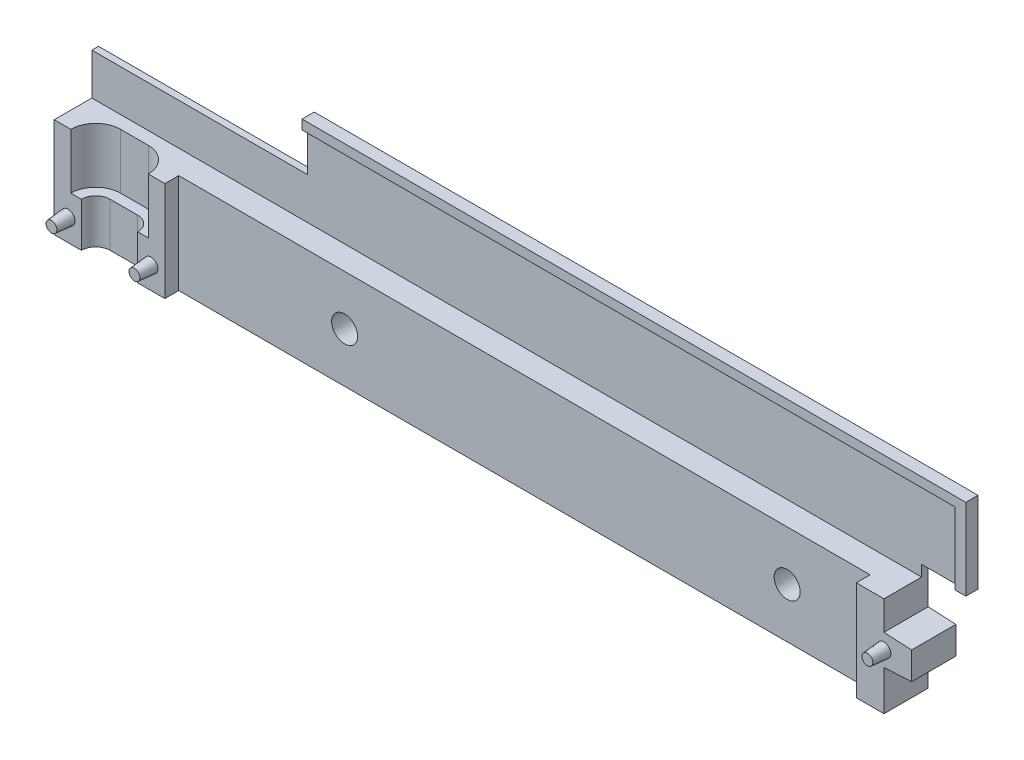
SolidWorks part; units mm, degrees
ref_plane "Front Plane" through (0, 0, 0) normal (0, 0, 1) x (1, 0, 0)
ref_plane "Top Plane" through (0, 0, 0) normal (0, 1, 0) x (1, 0, 0)
ref_plane "Right Plane" through (0, 0, 0) normal (1, 0, 0) x (0, 0, -1)
ref_axis "X-Axis" through (0, 0, 0) along (1, 0, 0)
ref_axis "Y-Axis" through (0, 42.2917, 0) along (0, -1, 0)
ref_axis "Z-Axis" through (0, 0, 55.0015) along (0, 0, -1)
sketch "Sketch1" plane through (0, 0, 0) normal (0, 0, 1) x (1, 0, 0)
  line L1 (-127.8191, -9.8629) -> (22.1809, -9.8629)
  line L2 (22.1809, -9.8629) -> (22.1809, -2.6129)
  line L3 (22.1809, -2.6129) -> (27.1809, -2.6129)
  line L4 (27.1809, -2.6129) -> (27.1809, 2.8871)
  line L5 (27.1809, 2.8871) -> (22.1809, 2.8871)
  line L6 (22.1809, 2.8871) -> (22.1809, 10.1371)
  line L7 (22.1809, 10.1371) -> (31.1809, 10.1371)
  line L8 (31.1809, 10.1371) -> (31.1809, 23.6371)
  line L10 (-127.8191, 15.6371) -> (-127.8191, -9.8629)
  line L12 (-88.8191, -25.8695) -> (-88.8191, 48.9262) construction
  line L13 (31.1809, 13.1371) -> (10.3885, 13.1371) construction
  line L14 (31.1809, 23.6371) -> (-88.8191, 23.6371) construction
  line L15 (-88.8191, 23.6371) -> (-88.8191, 15.6371)
  line L16 (-88.8191, 15.6371) -> (-127.8191, 15.6371)
  line L17 (31.1809, 23.6371) -> (31.1809, 24.8371)
  line L18 (31.1809, 24.8371) -> (-88.8191, 24.8371)
  line L19 (-88.8191, 24.8371) -> (-88.8191, 23.6371)
  point P5 (27.1809, 0.1371)
  dimension "D2" = 10
  dimension "D3" = 20
  dimension "D4" = 5.5
  dimension "D5" = 9
  dimension "D7" = 120
  dimension "D8" = 5
  dimension "D10" = 3
  dimension "D11" = 8
  dimension "D12" = 10.5
  dimension "D13" = 1.2
  dimension "D14" = 150
extrude "Boss-Extrude1" add sketch "Sketch1" along normal blind 8 and the other way blind 8
sketch "Sketch2" plane through (-127.8191, 0, 0) normal (-1, 0, 0) x (0, 0, 1)
  line L0 (-8, -9.8629) -> (8, -9.8629) construction
  line L1 (-6.8, 23.1371) -> (6.8, 23.1371) construction
  line L2 (-6.8, 23.1371) -> (-6.8, 8.1371)
  line L3 (-6.8, 8.1371) -> (6.8, 8.1371)
  line L4 (6.8, 23.1371) -> (6.8, 8.1371)
  line L5 (-8, 24.8371) -> (-8, 15.6371) construction
  line L7 (-8, 2.8871) -> (8, 2.8871) construction
  line L8 (-8, 15.6371) -> (-8, -9.8629) construction
  line L9 (8, 15.6371) -> (8, -9.8629) construction
  line L10 (0, 2.8871) -> (0, 23.1371) construction
  line L11 (-6.8, 23.1371) -> (-5.8, 23.1371)
  line L12 (-5.8, 23.1371) -> (-5.8, 24.8371)
  line L13 (-8, 24.8371) -> (8, 24.8371) construction
  line L14 (-5.8, 24.8371) -> (5.8, 24.8371)
  line L15 (5.8, 24.8371) -> (5.8, 23.1371)
  line L16 (5.8, 23.1371) -> (6.8, 23.1371)
  point P6 (0, 23.1371)
  dimension "D1" = 33
  dimension "D2" = 18
  dimension "D3" = 1
  dimension "D4" = 1
  dimension "D5" = 15
  dimension "D7" = 1.2
extrude "Cut-Extrude1" cut sketch "Sketch2" against normal offset from surface (157 mm away) 2 up to face at (31.1809, 17.4871, 0)
sketch "Sketch8" plane through (0, 0, 0) normal (0, 0, 1) x (1, 0, 0)
  line L0 (-127.8191, 15.6371) -> (-127.8191, -9.8629) construction
  line L1 (-107.8191, 24.8371) -> (17.1809, 24.8371)
  line L2 (-107.8191, 24.8371) -> (-107.8191, -9.8629)
  line L3 (-107.8191, -9.8629) -> (17.1809, -9.8629)
  line L4 (17.1809, 24.8371) -> (17.1809, -9.8629)
  line L5 (-127.8191, -9.8629) -> (22.1809, -9.8629) construction
  line L7 (22.1809, 2.8871) -> (22.1809, 10.1371) construction
  line L8 (29.1809, 24.8371) -> (-88.8191, 24.8371) construction
  point P12 (22.1809, 6.5121)
  dimension "D1" = 20
  dimension "D2" = 5
extrude "Cut-Extrude4" cut sketch "Sketch8" against normal blind 2.5 and the other way blind 2.5 contours L2 L3 L4 L1
sketch "Sketch9" plane through (0, 0, 0) normal (0, 0, 1) x (1, 0, 0)
  line L0 (-107.8191, -0.8629) -> (17.1809, -0.8629) construction
  line L1 (-107.8191, 8.1371) -> (-107.8191, -9.8629) construction
  line L2 (17.1809, 8.1371) -> (17.1809, -9.8629) construction
  circle A0 centre (-77.8191, -0.8629) radius 2.35
  circle A1 centre (2.1809, -0.8629) radius 2.35
  dimension "D1" = 4.7
  dimension "D2" = 80
  dimension "D3" = 15
extrude "Cut-Extrude5" cut sketch "Sketch9" against normal through all and the other way through all
chamfer "Chamfer2" distance 5 angle 3 2 edges at (27.1809, -2.6129, 0) (27.1809, 2.8871, 0) first distance on face at (24.6809, -2.6129, 0) first distance on face at (24.6809, 2.8871, 0)
sketch "Sketch14" plane through (0, 8.1371, 0) normal (0, 1, 0) x (1, 0, 0)
  line L0 (-120.3191, 4.5) -> (-115.3191, 4.5)
  line L1 (-115.3191, -4.5) -> (-120.3191, -4.5)
  line L2 (-107.8191, 0) -> (-127.8191, 0) construction
  line L3 (-107.8191, 2.5) -> (-107.8191, -2.5) construction
  line L5 (-127.8191, 6.8) -> (-127.8191, -6.8) construction
  arc A0 (-115.3191, 4.5) -> (-115.3191, -4.5) centre (-115.3191, 0) cw
  arc A1 (-120.3191, -4.5) -> (-120.3191, 4.5) centre (-120.3191, 0) cw
  point P16 (-117.8191, 0)
  dimension "D1" = 4.5
  dimension "D2" = 5
  dimension "D3" = 2.5
extrude "Cut-Extrude8" cut sketch "Sketch14" against normal blind 10
sketch "Sketch15" plane through (0, -1.8629, 0) normal (0, 1, 0) x (1, 0, 0)
  line L7 (-120.3191, -2.6) -> (-115.3191, -2.6)
  line L8 (-115.3191, 2.6) -> (-120.3191, 2.6)
  arc A2 (-120.3191, 4.5) -> (-120.3191, -4.5) centre (-120.3191, 0) ccw construction
  arc A3 (-115.3191, -4.5) -> (-115.3191, 4.5) centre (-115.3191, 0) ccw construction
  arc A6 (-120.3191, 2.6) -> (-120.3191, -2.6) centre (-120.3191, 0) ccw
  arc A7 (-115.3191, -2.6) -> (-115.3191, 2.6) centre (-115.3191, 0) ccw
  dimension "D2" = 2.6
extrude "Cut-Extrude9" cut sketch "Sketch15" against normal through all
sketch "Sketch16" plane through (0, 0, 0) normal (0, 0, 1) x (1, 0, 0)
  line L1 (-137.4451, 59.0989) -> (76.8996, 59.0989)
  line L2 (-137.4451, 59.0989) -> (-137.4451, -25.5467)
  line L3 (-137.4451, -25.5467) -> (76.8996, -25.5467)
  line L4 (76.8996, 59.0989) -> (76.8996, -25.5467)
extrude "Cut-Extrude10" cut sketch "Sketch16" along normal through all
sketch "Sketch17" plane through (0, 0, 0) normal (0, 0, 1) x (1, 0, 0)
  line L1 (31.1809, 24.8371) -> (29.1809, 24.8371)
  line L2 (31.1809, 24.8371) -> (31.1809, 10.1371)
  line L3 (31.1809, 10.1371) -> (29.1809, 10.1371)
  line L4 (29.1809, 24.8371) -> (29.1809, 10.1371)
extrude "Cut-Extrude11" cut sketch "Sketch17" against normal up to surface (5.8 mm away) up to face at (-29.8191, 23.9871, -5.8)
sketch "Sketch19" plane through (0, 0, 0) normal (0, 0, 1) x (1, 0, 0)
  line L0 (17.1809, 0.1371) -> (27.1809, 0.1371) construction
  line L1 (27.1809, 2.6251) -> (27.1809, -2.3509) construction
  line L3 (-125.3191, -5.8629) -> (-110.3191, -5.8629) construction
  line L5 (-117.8191, -9.8629) -> (-117.8191, -1.8629) construction
  line L8 (17.1809, 8.1371) -> (17.1809, -9.8629) construction
  line L11 (-115.3191, -9.8629) -> (-120.3191, -9.8629) construction
  line L12 (-115.3191, -1.8629) -> (-120.3191, -1.8629) construction
  circle A0 centre (-125.3191, -5.8629) radius 1.25
  circle A1 centre (-110.3191, -5.8629) radius 1.25
  circle A2 centre (22.1809, 0.1371) radius 1.25
  point P17 (-117.8191, -5.8629)
  dimension "D2" = 2.5
  dimension "D1" = 15
extrude "Boss-Extrude5" add sketch "Sketch19" along normal blind 3 separate body
chamfer "Chamfer3" distance 3 angle 5 1 edges at (23.4309, 0.1371, 3) first distance on face at (23.4309, 0.1371, 3)
chamfer "Chamfer4" distance 3 angle 5 1 edges at (-109.0691, -5.8629, 3) first distance on face at (-109.0691, -5.8629, 3)
chamfer "Chamfer5" distance 3 angle 5 1 edges at (-124.0691, -5.8629, 3) first distance on face at (-124.0691, -5.8629, 3)
equation "\"Largeur Bande\"= 12.3"
equation "\"Largeur Feeder\"= \"Largeur Rail\" + 1.2 + 1.2 + 0.3"
equation "\"Largeur Rail\"= \"Largeur Bande\" + 1"
equation "\"D1@Boss-Extrude1\"=\"Largeur Feeder\"/2"
equation "\"D2@Boss-Extrude1\"=\"Largeur Feeder\"/2"
